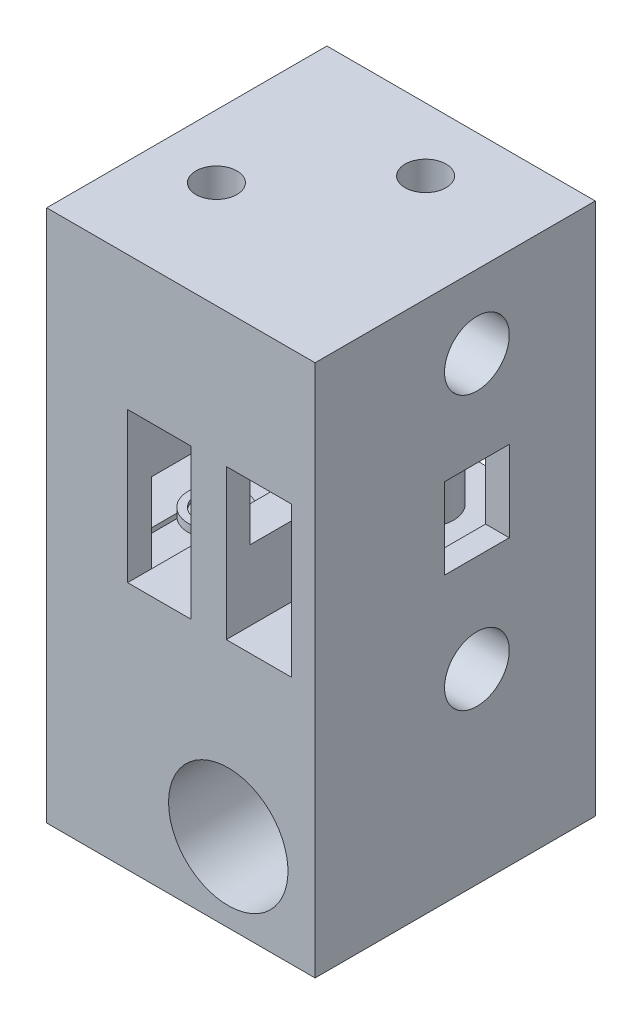
SolidWorks part; units mm, degrees
ref_plane "Front Plane" through (0, 0, 0) normal (0, 0, 1) x (1, 0, 0)
ref_plane "Top Plane" through (0, 0, 0) normal (0, 1, 0) x (1, 0, 0)
ref_plane "Right Plane" through (0, 0, 0) normal (1, 0, 0) x (0, 0, -1)
sketch "Top-Sketch1" plane through (0, 0, 0) normal (0, 1, 0) x (1, 0, 0)
  line L1 (0, 0) -> (34, 0)
  line L2 (0, 0) -> (0, 35.5)
  line L3 (0, 35.5) -> (34, 35.5)
  line L4 (34, 0) -> (34, 35.5)
  circle A2 centre (8, 13.5) radius 2.6
  circle A3 centre (20.5, 27.5) radius 2.6
  dimension "D3" = 5.2
  dimension "D1" = 13.5
  dimension "D2" = 12.5
  dimension "D4" = 14
  dimension "D6" = 8
  dimension "D11" = 35.5
  dimension "D5" = 8
  dimension "D7" = 13.5
extrude "Boss-Extrude4" add sketch "Top-Sketch1" along normal blind 17
sketch "TopRightRiser" plane through (0, 0, 0) normal (0, -1, 0) x (1, 0, 0)
  line L0 (5.75, -10.7541) -> (5.75, 0)
  line L1 (0, 0) -> (34, 0) construction
  line L2 (5.75, 0) -> (10.25, 0)
  line L3 (10.25, 0) -> (10.25, -10.7541)
  arc A0 (5.75, -10.7541) -> (10.25, -10.7541) centre (8, -13.5) ccw
  circle A1 centre (8, -13.5) radius 2.6 construction
  circle A2 centre (8, -13.5) radius 2.6
  point P13 (8, 0)
  dimension "D1" = 7.1
  dimension "D2" = 4.5
extrude "TopRightRiserBoss-Extrude5" add sketch "TopRightRiser" along normal blind 9.9
sketch "TopLeft" plane through (0, 0, 0) normal (0, -1, 0) x (1, 0, 0)
  line L0 (18.25, -24.7541) -> (18.25, 0)
  line L1 (10.25, 0) -> (34, 0) construction
  line L2 (18.25, 0) -> (22.75, 0)
  line L3 (22.75, 0) -> (22.75, -24.7541)
  line L4 (10.25, 0) -> (5.75, 0) construction
  circle A0 centre (20.5, -27.5) radius 2.6
  circle A1 centre (20.5, -27.5) radius 2.6 construction
  arc A2 (18.25, -24.7541) -> (22.75, -24.7541) centre (20.5, -27.5) ccw
  arc A3 (5.75, -10.7541) -> (10.25, -10.7541) centre (8, -13.5) ccw construction
  point P16 (20.5, 0)
extrude "TopLeftBoss-Extrude6" add sketch "TopLeft" along normal blind 0.4
sketch "MidWall" plane through (0, 0, 0) normal (0, -1, 0) x (-1, 0, 0)
  line L0 (-10.25, 10.7541) -> (-10.25, 0) construction
  line L1 (0, 3) -> (-10.25, 3)
  line L2 (0, 3) -> (0, 0)
  line L3 (0, 0) -> (-10.25, 0)
  line L4 (-10.25, 3) -> (-10.25, 0)
  line L5 (0, 35.5) -> (0, 0) construction
  line L6 (-10.25, 0) -> (-5.75, 0) construction
  line L7 (-18.25, 0) -> (-18.25, 24.7541) construction
  line L8 (-18.25, 0) -> (-22.75, 0)
  line L9 (-18.25, 0) -> (-18.25, 3)
  line L10 (-18.25, 3) -> (-22.75, 3)
  line L11 (-22.75, 0) -> (-22.75, 3)
  line L12 (-22.75, 24.7541) -> (-22.75, 0) construction
  line L13 (-10.25, 0) -> (-18.25, 0) construction
  line L14 (-22.75, 0) -> (-34, 0) construction
  line L15 (-31, 0) -> (-34, 0)
  line L16 (-31, 0) -> (-31, 35.5)
  line L17 (-31, 35.5) -> (-34, 35.5)
  line L18 (-34, 0) -> (-34, 35.5)
  line L19 (-34, 35.5) -> (0, 35.5) construction
  line L20 (-34, 0) -> (-34, 35.5) construction
extrude "MidWallBoss-Extrude7" add sketch "MidWall" along normal blind 19
sketch "Bottom" plane through (0, -19, 0) normal (0, -1, 0) x (1, 0, 0)
  line L0 (0, 0) -> (34, 0) construction
  line L1 (0, 0) -> (34, 0)
  line L2 (0, 0) -> (0, -35.5)
  line L3 (0, -35.5) -> (34, -35.5)
  line L4 (34, 0) -> (34, -35.5)
  line L5 (34, 0) -> (34, -35.5) construction
  line L6 (0, -35.5) -> (0, 0) construction
extrude "BottomBoss-Extrude8" add sketch "Bottom" along normal blind 31.5
sketch "LowerRight" plane through (0, -19, 0) normal (0, 1, 0) x (1, 0, 0)
  line L0 (5.75, 10.7541) -> (5.75, 3)
  line L1 (5.75, 3) -> (10.25, 3)
  line L2 (10.25, 3) -> (10.25, 10.7541)
  line L6 (10.25, 10.7541) -> (10.25, 3) construction
  line L7 (5.75, 3) -> (5.75, 10.7541) construction
  line L8 (10.25, 3) -> (5.75, 3) construction
  circle A0 centre (8, 13.5) radius 2.6
  arc A1 (10.25, 10.7541) -> (5.75, 10.7541) centre (8, 13.5) ccw
  circle A2 centre (8, 13.5) radius 2.6 construction
  arc A3 (10.25, 10.7541) -> (5.75, 10.7541) centre (8, 13.5) ccw construction
extrude "LowerRightRightBoss-Extrude10" add sketch "LowerRight" along normal blind 0.4
sketch "LowerLeft" plane through (0, -19, 0) normal (0, 1, 0) x (1, 0, 0)
  line L1 (18.25, 0) -> (22.75, 0)
  line L5 (0, 0) -> (34, 0) construction
  line L6 (18.25, 24.7541) -> (18.25, 0)
  line L7 (22.75, 24.7541) -> (22.75, 0)
  circle A0 centre (20.5, 27.5) radius 2.6
  arc A1 (22.75, 24.7541) -> (18.25, 24.7541) centre (20.5, 27.5) ccw
  circle A2 centre (20.5, 27.5) radius 2.6 construction
  arc A3 (22.75, 24.7541) -> (18.25, 24.7541) centre (20.5, 27.5) ccw construction
  point P3 (20.5, 0)
  dimension "D1" = 4.5
extrude "LowerLeftRiserBoss-Extrude9" add sketch "LowerLeft" along normal blind 9.9
sketch "TopRightInset-Sketch1" plane through (0, -9.9, 0) normal (0, -1, 0) x (1, 0, 0)
  line L0 (5.75, -10.7541) -> (5.75, -3)
  line L1 (5.75, -3) -> (10.25, -3)
  line L2 (10.25, -3) -> (10.25, -10.7541)
  line L3 (5.75, -10.7541) -> (5.75, -3) construction
  line L4 (5.75, -3) -> (10.25, -3) construction
  line L5 (10.25, -3) -> (10.25, -10.7541) construction
  arc A0 (10.25, -10.7541) -> (5.75, -10.7541) centre (8, -13.5) ccw
  arc A1 (5.75, -10.7541) -> (10.25, -10.7541) centre (8, -13.5) ccw construction
extrude "TopRightInset-Cut-Extrude1" cut sketch "TopRightInset-Sketch1" against normal blind 1
sketch "TopLeftInset-Sketch2" plane through (0, -0.4, 0) normal (0, -1, 0) x (1, 0, 0)
  line L0 (18.25, -24.7541) -> (18.25, -3)
  line L1 (18.25, -3) -> (22.75, -3)
  line L2 (22.75, -3) -> (22.75, -24.7541)
  line L3 (22.75, -3) -> (18.25, -3) construction
  line L4 (22.75, -24.7541) -> (22.75, -3) construction
  line L5 (18.25, -24.7541) -> (18.25, -3) construction
  arc A0 (22.75, -24.7541) -> (18.25, -24.7541) centre (20.5, -27.5) ccw
  arc A1 (18.25, -24.7541) -> (22.75, -24.7541) centre (20.5, -27.5) ccw construction
extrude "TopLeftInset-Cut-Extrude2" cut sketch "TopLeftInset-Sketch2" against normal blind 1
sketch "LowerLeftInset-Sketch3" plane through (0, -9.1, 0) normal (0, 1, 0) x (1, 0, 0)
  line L0 (18.25, 24.7541) -> (18.25, 3)
  line L1 (18.25, 3) -> (22.75, 3)
  line L2 (22.75, 3) -> (22.75, 24.7541)
  line L3 (22.75, 3) -> (18.25, 3) construction
  line L4 (18.25, 24.7541) -> (18.25, 3) construction
  line L5 (22.75, 3) -> (22.75, 24.7541) construction
  arc A0 (18.25, 24.7541) -> (22.75, 24.7541) centre (20.5, 27.5) ccw
  arc A1 (22.75, 24.7541) -> (18.25, 24.7541) centre (20.5, 27.5) ccw construction
extrude "LowerLeftInset-Cut-Extrude3" cut sketch "LowerLeftInset-Sketch3" against normal blind 1
sketch "LowerRightInset-Sketch4" plane through (0, -18.6, 0) normal (0, 1, 0) x (1, 0, 0)
  line L0 (5.75, 10.7541) -> (5.75, 3)
  line L1 (5.75, 3) -> (10.25, 3)
  line L2 (10.25, 3) -> (10.25, 10.7541)
  line L3 (10.25, 3) -> (5.75, 3) construction
  line L4 (5.75, 3) -> (5.75, 10.7541) construction
  line L5 (10.25, 10.7541) -> (10.25, 3) construction
  arc A0 (5.75, 10.7541) -> (10.25, 10.7541) centre (8, 13.5) ccw
  arc A1 (10.25, 10.7541) -> (5.75, 10.7541) centre (8, 13.5) ccw construction
extrude "LowerRightInsetCut-Extrude4" cut sketch "LowerRightInset-Sketch4" against normal blind 1
sketch "LM8UUHoleSketch1" plane through (0, 0, -35.5) normal (0, 0, -1) x (-1, 0, 0)
  line L0 (-34, 17) -> (-34, -50.5) construction
  line L2 (0, -19) -> (-31, -19) construction
  circle A0 centre (-23, -40.5) radius 7.5625
  dimension "D1" = 15.125
  dimension "D2" = 11
  dimension "D3" = 21.5
extrude "LM8UUCut-Extrude1" cut sketch "LM8UUHoleSketch1" against normal through all
sketch "XAxisRodSketch2" plane through (0, 0, 0) normal (-1, 0, 0) x (0, 0, 1)
  line L2 (-13.5, 17) -> (-13.5, -9.9) construction
  line L3 (-35.5, 0) -> (-3, 0) construction
  circle A0 centre (-20.5, -26.85) radius 4.1
  circle A1 centre (-20.5, 7.75) radius 4.1
  dimension "D1" = 8.2
  dimension "D5" = 34.6
  dimension "D4" = 7.75
  dimension "D2" = 7
extrude "XAxisRodCut-Extrude2" cut sketch "XAxisRodSketch2" against normal through all
sketch "Sketch3" plane through (34, 0, 0) normal (1, 0, 0) x (0, 0, -1)
  line L1 (24.6, -14.5) -> (16.4, -14.5)
  line L2 (24.6, -14.5) -> (24.6, -4.25)
  line L3 (24.6, -4.25) -> (16.4, -4.25)
  line L4 (16.4, -14.5) -> (16.4, -4.25)
  circle A0 centre (20.5, 7.75) radius 4.1 construction
  dimension "D1" = 12
  dimension "D3" = 10.25
extrude "BackHoleCutCut-Extrude3" cut sketch "Sketch3" against normal up to next
sketch "SteelShaftPushPinHoleSketch4" plane through (0, -50.5, 0) normal (0, -1, 0) x (1, 0, 0)
  circle A0 centre (8, -13.5) radius 2
  circle A1 centre (20.5, -27.5) radius 2
  dimension "D1" = 4
extrude "SteelShaftpushPinHoleCut-Extrude1" cut sketch "SteelShaftPushPinHoleSketch4" against normal through all
sketch "LM8UUM3FastenerSketch4" plane through (0, -50.5, 0) normal (0, -1, 0) x (1, 0, 0)
  line L0 (34, -20.5) -> (0, -20.5) construction
  line L2 (23, 0) -> (23, -35.5) construction
  circle A0 centre (14.4, -20.5) radius 2.1
  dimension "D2" = 4.2
  dimension "D1" = 8.6
extrude "LM8UUM3FastenerCut-Extrude1" cut sketch "LM8UUM3FastenerSketch4" against normal blind 15
equation "\"GABWidth\"= \"GABDistanceFromBackToFirstPulley\" + \"GABPulleyWDistanceBetween\" + \"GABDistanceFromPulleyToOutside\"'Equals 35.5"
equation "\"GABLowerHeight\"= 31.5mm"
equation "\"GABUpperHeight\"= 17mm'From the100"
equation "\"GABMidWallHeight\"= 19mm'From the100"
equation "\"StandardWallThickness\"= 3mm"
equation "\"GABMidShortRiserHeight\"= \"GABMidWallHeight\" / 2 - \"20TGT2PulleyWidth\"'Equals 0.8"
equation "\"GABMidLongRiserHeight\"= \"GABMidWallHeight\" - \"GABMidShortRiserHeight\" - \"20TGT2PulleyWidth\"'Equals 9.5"
equation "\"GABDistanceFromBackToFirstPulley\"= \"StandardWallThickness\" + 10.5mm"
equation "\"GABPulleyDDistanceBetween\"= 12.5mm'From the100"
equation "\"GABPulleyWDistanceBetween\"= \"SteelShaft5mmHoleDiameter\" + \"RodShaft8mmDiameter\" + 1mm'the100 has this as 12.5. Increase to 14 so XAxis rod fits between"
equation "\"SteelShaft5mmHoleDiameter\"= 5mm"
equation "\"20TGT2PulleyWidth\"= 8.7mm'The STL of the Pulley in the diagram is a bit larger"
equation "\"7mmx1mmSpacerDiameter\"= 7mm + .1mm'Add .1mm for printing"
equation "\"7mmx1mmSpacerHeight\"= 1mm"
equation "\"GABRiserBossOffset\"= 0.4mm'Aligns Pulleys inside edges to be 2.5mm (.5mm apart top to bottom)"
equation "\"D2@Top-Sketch1\" = \"GABPulleyDDistanceBetween\""
equation "\"D3@Top-Sketch1\" = \"SteelShaft5mmHoleDiameter\" + .2mm"
equation "\"D4@Top-Sketch1\" = \"GABPulleyWDistanceBetween\""
equation "\"D1@Boss-Extrude4\"=\"GABUpperHeight\""
equation "\"D1@TopRightRiserBoss-Extrude5\" = \"GABMidLongRiserHeight\" + \"GABRiserBossOffset\""
equation "\"D1@TopLeftBoss-Extrude6\" = \"GABMidShortRiserHeight\" - \"GABRiserBossOffset\""
equation "\"D1@MidWall\" = \"StandardWallThickness\""
equation "\"D1@MidWallBoss-Extrude7\" = \"GABMidWallHeight\""
equation "\"D1@BottomBoss-Extrude8\" = \"GABLowerHeight\""
equation "\"D1@LowerLeftRiserBoss-Extrude9\" = \"GABMidLongRiserHeight\" + \"GABRiserBossOffset\""
equation "\"D1@LowerRightRightBoss-Extrude10\" = \"GABMidShortRiserHeight\" - \"GABRiserBossOffset\""
equation "\"D1@TopRightInset-Cut-Extrude1\" = \"7mmx1mmSpacerHeight\""
equation "\"D1@TopLeftInset-Cut-Extrude2\" = \"7mmx1mmSpacerHeight\""
equation "\"D1@LowerRightInsetCut-Extrude4\" = \"7mmx1mmSpacerHeight\""
equation "\"D1@TopRightRiser\"=\"7mmx1mmSpacerDiameter\""
equation "\"LM8UUDiameter\"= 15mm"
equation "\"D1@LM8UUHoleSketch1\"=\"LM8UUDiameter\" +.125mm"
equation "\"LM8UUOffsetFromGABBack\"= 11mm'From the100"
equation "\"D2@LM8UUHoleSketch1\"=\"LM8UUOffsetFromGABBack\""
equation "\"RodShaft8mmDiameter\"= 8mm"
equation "\"D1@XAxisRodSketch2\" = \"RodShaft8mmDiameter\" + .2mm"
equation "\"GABDistanceBetweenXAxisRods\"= 34.6mm'From the100"
equation "\"D5@XAxisRodSketch2\" = \"GABDistanceBetweenXAxisRods\""
equation "\"LM8UUOffsetFromBottomMidSection\"= 21.5mm'From the100"
equation "\"D3@LM8UUHoleSketch1\"=\"LM8UUOffsetFromBottomMidSection\""
equation "\"XAxisRodDistanceFromTopMidSection\"= 7.75mm'From the100"
equation "\"D4@XAxisRodSketch2\"=\"XAxisRodDistanceFromTopMidSection\""
equation "\"D1\"= \"GABXAxisRodDepth\""
equation "\"D1@SteelShaftPushPinHoleSketch4\"=\"SteelPushPinHoleDiameter\""
equation "\"D1@LM8UUM3FastenerSketch4\"=\"LM8UUDiameter\" /2 + \"LM8UUFasteningHoleDiameter\" / 2 - 1mm"
equation "\"D2@LM8UUM3FastenerSketch4\"=\"LM8UUFasteningHoleDiameter\""
equation "\"LM8UUFasteningHoleDiameter\"= 4.2mm'10/24 set screw hole diameter"
equation "\"D1\"= \"LM8UUDiameter\""
equation "\"GABDistanceFromPulleyToOutside\"= 8mm'the100 has this as 12.5. Decrease to 8 so WDistanceBetween can be increased"
equation "\"D2@XAxisRodSketch2\"=\"GABPulleyWDistanceBetween\"/2"
equation "\"D1@LM8UUM3FastenerCut-Extrude1\"=\"LM8UUDiameter\""
equation "\"D5@Top-Sketch1\"=\"GABDistanceFromPulleyToOutside\""
equation "\"D6@Top-Sketch1\"=\"GABDistanceFromPulleyToOutside\""
equation "\"D11@Top-Sketch1\"=\"GABWidth\""
equation "\"D1@Top-Sketch1\"=\"GABDistanceFromBackToFirstPulley\""
equation "\"SteelPushPinHoleDiameter\"= \"SteelShaft5mmHoleDiameter\" - 1mm"
